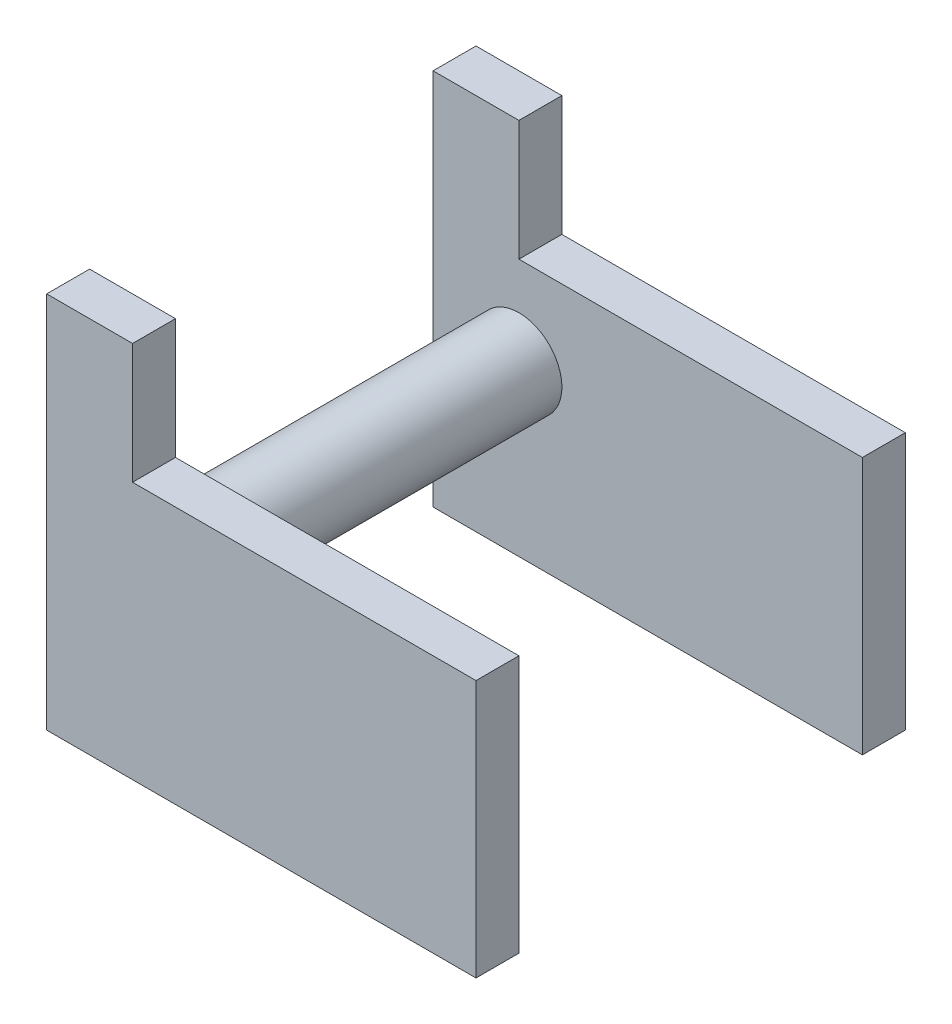
SolidWorks part; units mm, degrees
ref_plane "Front Plane" through (0, 0, 0) normal (0, 0, 1) x (1, 0, 0)
ref_plane "Top Plane" through (0, 0, 0) normal (0, 1, 0) x (1, 0, 0)
ref_plane "Right Plane" through (0, 0, 0) normal (1, 0, 0) x (0, 0, -1)
sketch "Sketch1" plane through (0, 0, 0) normal (0, 0, 1) x (1, 0, 0)
  line L1 (0, 0) -> (-31.75, 0)
  line L2 (0, 0) -> (0, 19.05)
  line L3 (0, 19.05) -> (-25.4, 19.05)
  line L4 (-31.75, 0) -> (-31.75, 6.35)
  line L6 (-31.75, 6.35) -> (-31.75, 27.94)
  line L7 (-31.75, 27.94) -> (-25.4, 27.94)
  line L8 (-25.4, 19.05) -> (-25.4, 27.94)
  dimension "D1" = 31.75
  dimension "D2" = 21.59
  dimension "D3" = 19.05
  dimension "D4" = 6.35
extrude "Boss-Extrude1" add sketch "Sketch1" along normal blind 31.75
sketch "Sketch2" plane through (0, 27.94, 0) normal (0, 1, 0) x (1, 0, 0)
  line L0 (-31.75, -31.75) -> (-31.75, 0) construction
  line L1 (-31.75, -3.175) -> (0, -3.175)
  line L2 (-31.75, -3.175) -> (-31.75, -28.575)
  line L3 (-31.75, -28.575) -> (0, -28.575)
  line L4 (0, -3.175) -> (0, -28.575)
  line L5 (0, -31.75) -> (0, 0) construction
  line L6 (-25.4, -31.75) -> (-31.75, -31.75) construction
  dimension "D1" = 25.4
  dimension "D2" = 3.175
extrude "Cut-Extrude1" cut sketch "Sketch2" against normal up to surface (27.94 mm away) up to face at (-15.875, 0, 15.875)
sketch "Sketch3" plane through (0, 0, 3.175) normal (0, 0, 1) x (1, 0, 0)
  line L0 (-31.75, 0) -> (-31.75, 27.94) construction
  line L2 (-31.75, 0) -> (0, 0) construction
  circle A1 centre (-25.4, 12.446) radius 3.175
  dimension "D4" = 6.35
  dimension "D5" = 12.446
  dimension "D6" = 6.35
extrude "Boss-Extrude2" add sketch "Sketch3" along normal up to surface (25.4 mm away) up to face at (-19.05, 15.6633, 28.575)
